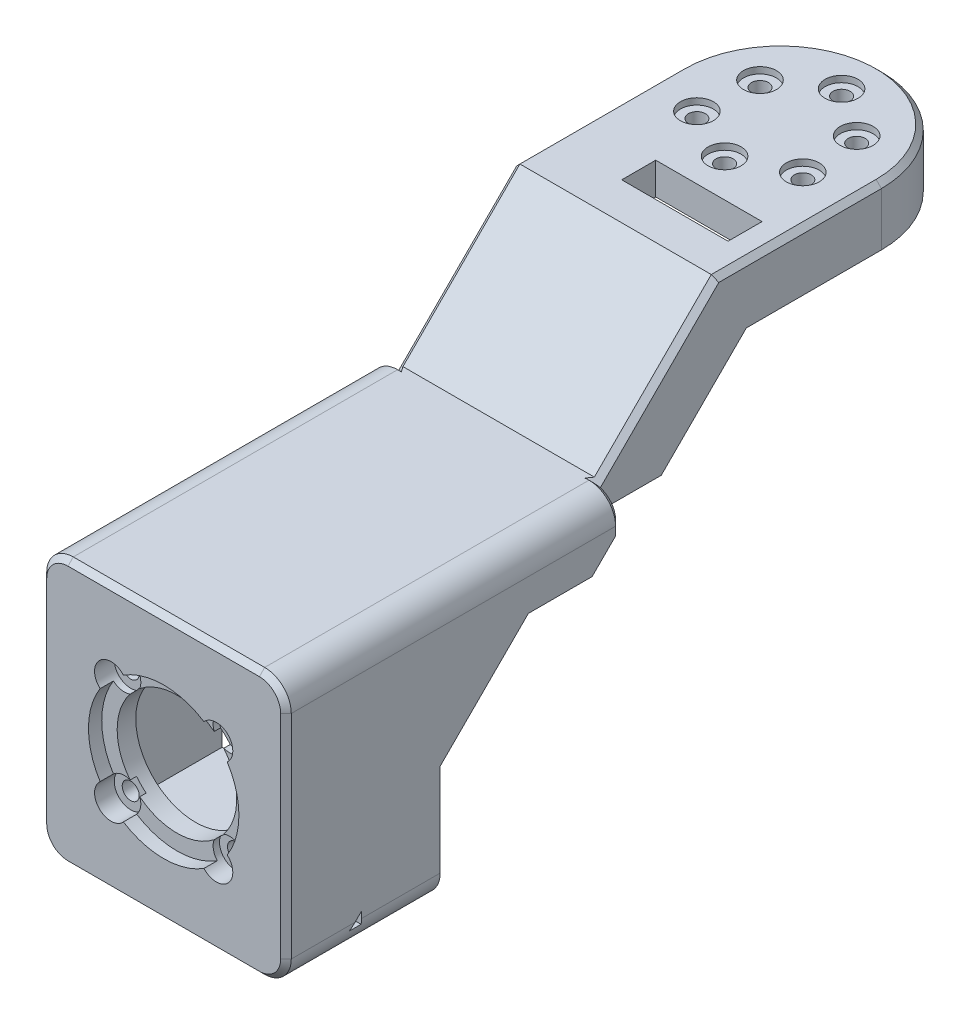
SolidWorks part; units mm, degrees
ref_plane "前视基准面" through (0, 0, 0) normal (0, 0, 1) x (1, 0, 0)
ref_plane "上视基准面" through (0, 0, 0) normal (0, 1, 0) x (1, 0, 0)
ref_plane "右视基准面" through (0, 0, 0) normal (1, 0, 0) x (0, 0, -1)
other "Configuration Table"
sketch "草图1" plane through (0, 0, 0) normal (0, 1, 0) x (1, 0, 0)
  circle A0 centre (0, 0) radius 19
  dimension "D1" = 38
extrude "凸台-拉伸1" add sketch "草图1" along normal blind 6
sketch "草图2" plane through (0, 6, 0) normal (0, 1, 0) x (1, 0, 0)
  line L0 (-19, 0) -> (19, 0) construction
  line L2 (-19, 0) -> (19, 0)
  line L3 (-19, 0) -> (-19, -25)
  line L4 (-19, -25) -> (19, -25)
  line L5 (19, 0) -> (19, -25)
  circle A0 centre (0, 0) radius 19 construction
  dimension "D1" = 25
extrude "凸台-拉伸2" add sketch "草图2" against normal up to surface (6 mm away) up to face at (0, 0, 19)
sketch "草图3" plane through (0, 6, 0) normal (0, 1, 0) x (1, 0, 0)
  line L1 (-19, -25) -> (19, -25)
  line L2 (-19, -25) -> (-19, -31)
  line L3 (-19, -31) -> (19, -31)
  line L4 (19, -25) -> (19, -31)
  dimension "D1" = 6
extrude "凸台-拉伸3" add sketch "草图3" against normal blind 28
sketch "草图4" plane through (0, 0, 31) normal (0, 0, 1) x (1, 0, 0)
  line L0 (19, -22) -> (19, 6) construction
  line L1 (-19, -22) -> (19, -22)
  line L2 (-19, -22) -> (-19, -16)
  line L3 (-19, -16) -> (19, -16)
  line L4 (19, -22) -> (19, -16)
  dimension "D1" = 6
extrude "凸台-拉伸4" add sketch "草图4" along normal blind 85
sketch "草图5" plane through (0, -22, 0) normal (0, -1, 0) x (1, 0, 0)
  line L0 (19, 116) -> (19, 25) construction
  line L1 (-19, 116) -> (19, 116)
  line L2 (-19, 116) -> (-19, 110)
  line L3 (-19, 110) -> (19, 110)
  line L4 (19, 116) -> (19, 110)
  dimension "D1" = 6
extrude "凸台-拉伸5" add sketch "草图5" along normal blind 40
sketch "草图6" plane through (0, 0, 0) normal (0, -1, 0) x (1, 0, 0)
  line L0 (-14.15, 0) -> (-14.15, 25)
  line L1 (19, 25) -> (-19, 25) construction
  line L2 (14.15, 0) -> (14.15, 25)
  line L3 (14.15, 25) -> (-14.15, 25)
  circle A0 centre (0, 0) radius 14.15
  arc M2 (-19, 0) -> (19, 0) centre (0, 0) ccw
  line M3 (19, 0) -> (19, 25)
  line M4 (19, 25) -> (-19, 25)
  line M5 (-19, 25) -> (-19, 0)
  dimension "D1" = 28.3
extrude "凸台-拉伸6" add sketch "草图6" along normal blind 6 contours A0 L0 L2 M4 M5 M2 M3 region at (0, 0, -14.7314)
sketch "草图7" plane through (-19, 0, 0) normal (-1, 0, 0) x (0, 0, 1)
  line L0 (31, 6) -> (53, -16)
  line L1 (116, -16) -> (31, -16) construction
  line L2 (53, -16) -> (31, -16)
  line L3 (31, -16) -> (31, 6)
sketch "草图8" plane through (19, 0, 0) normal (1, 0, 0) x (0, 0, -1)
  line L3 (-31, 6) -> (-53, -16)
  line L4 (-53, -16) -> (-31, -16)
  line L5 (-31, -16) -> (-31, 6)
  line L6 (-31, 6) -> (-53, -16)
  line L7 (-53, -16) -> (-31, -16)
  line L8 (-31, -16) -> (-31, 6)
  dimension "D1" = 0
extrude "凸台-拉伸8" add sketch "草图8" against normal up to surface (38 mm away) up to face at (-19, -20, 56.4)
sketch "草图11" plane through (0, 0, 110) normal (0, 0, -1) x (-1, 0, 0)
  line L0 (0, -22) -> (0, -41.5) construction
  line L1 (19, -22) -> (-19, -22) construction
  circle A0 centre (0, -41.5) radius 11.25
  dimension "D2" = 22.5
  dimension "D1" = 19.5
extrude "切除-拉伸2" cut sketch "草图11" against normal through all
sketch "草图12" plane through (0, 0, 116) normal (0, 0, 1) x (1, 0, 0)
  line L0 (0, -41.5) -> (9.8995, -31.6005) construction
  line L1 (0, -41.5) -> (14.2465, -41.5) construction
  circle A0 centre (9.8995, -31.6005) radius 1.6
  circle A1 centre (9.8995, -51.3995) radius 1.6
  circle A2 centre (-9.8995, -51.3995) radius 1.6
  circle A3 centre (-9.8995, -31.6005) radius 1.6
  point P13 (0, -41.5)
  dimension "D2" = 3.2
  dimension "D1" = 14
  dimension "D4" = 45
  dimension "D3" = 4
extrude "切除-拉伸3" cut sketch "草图12" against normal through all
sketch "草图13" plane through (0, 0, 116) normal (0, 0, 1) x (1, 0, 0)
  line L0 (0, -41.5) -> (11.25, -41.5) construction
  circle A0 centre (-9.8995, -31.6005) radius 3.1
  circle A1 centre (0, -41.5) radius 11.25 construction
  circle A2 centre (9.8995, -31.6005) radius 3.1
  circle A3 centre (9.8995, -51.3995) radius 3.1
  circle A4 centre (-9.8995, -51.3995) radius 3.1
  point P17 (0, -41.5)
  dimension "D1" = 6.2
  dimension "D2" = 4
extrude "切除-拉伸4" cut sketch "草图13" against normal blind 3.7
sketch "草图14" plane through (0, 0, 116) normal (0, 0, 1) x (1, 0, 0)
  circle A0 centre (0, -41.5) radius 14.15
  dimension "D1" = 28.3
extrude "切除-拉伸5" cut sketch "草图14" against normal blind 2.5
sketch "草图15" plane through (19, 0, 0) normal (1, 0, 0) x (0, 0, -1)
  line L0 (-110, -22) -> (-110, -62) construction
  line L2 (-110, -62) -> (-104, -62)
  line L3 (-104, -62) -> (-70, -28)
  line L4 (-70, -28) -> (-70, -22)
  line L5 (-110, -22) -> (-25, -22) construction
  line L6 (-70, -22) -> (-110, -22) construction
  line L7 (-110, -62) -> (-116, -62)
  line L8 (-116, -62) -> (-116, -16)
  line L9 (-116, -16) -> (-53, -16) construction
  line L10 (-116, -16) -> (-70, -16)
  line L11 (-70, -16) -> (-70, -22)
  dimension "D1" = 6
extrude "凸台-拉伸12" add sketch "草图15" along normal blind 4
sketch "草图16" plane through (-19, 0, 0) normal (-1, 0, 0) x (0, 0, 1)
  line L7 (104, -62) -> (110, -62)
  line L8 (70, -28) -> (104, -62)
  line L9 (70, -22) -> (70, -28)
  line L10 (70, -16) -> (70, -22)
  line L11 (116, -16) -> (70, -16)
  line L12 (116, -62) -> (116, -16)
  line L13 (110, -62) -> (116, -62)
  line L14 (104, -62) -> (110, -62)
  line L15 (70, -28) -> (104, -62)
  line L16 (70, -22) -> (70, -28)
  line L17 (70, -16) -> (70, -22)
  line L18 (116, -16) -> (70, -16)
  line L19 (116, -62) -> (116, -16)
  line L20 (110, -62) -> (116, -62)
  dimension "D1" = 0
extrude "凸台-拉伸13" add sketch "草图16" along normal blind 4
sketch "草图18" plane through (-19, 0, 0) normal (-1, 0, 0) x (0, 0, 1)
  line L1 (25, -6) -> (41, -22)
  line L2 (25, -22) -> (70, -22) construction
  line L3 (31, 6) -> (53, -16) construction
  line L4 (41, -22) -> (41.8531, -34.2873)
  line L5 (41.8531, -34.2873) -> (18.4073, -35.915)
  line L6 (18.4073, -35.915) -> (21.1184, -13.0175)
  line L7 (21.1184, -13.0175) -> (25, -6)
extrude "切除-拉伸7" cut sketch "草图18" against normal through all
sketch "草图19" plane through (0, -62, 0) normal (0, -1, 0) x (1, 0, 0)
  line L0 (23, 104) -> (23, 70) construction
  line L1 (-23, 116) -> (23, 116)
  line L2 (-23, 116) -> (-23, 86)
  line L3 (-23, 86) -> (23, 86)
  line L4 (23, 116) -> (23, 86)
  dimension "D1" = 30
extrude "凸台-拉伸14" add sketch "草图19" along normal blind 4
sketch "草图20" plane through (-23, 0, 0) normal (-1, 0, 0) x (0, 0, 1)
  line L1 (86, -66) -> (102.3181, -66)
  line L2 (86, -66) -> (86, -36.6886)
  line L3 (86, -36.6886) -> (102.3181, -36.6886)
  line L4 (102.3181, -66) -> (102.3181, -36.6886)
extrude "凸台-拉伸15" add sketch "草图20" against normal up to surface (4 mm away) up to face at (-19, -39.2, 92.8)
sketch "草图21" plane through (23, 0, 0) normal (1, 0, 0) x (0, 0, -1)
  line L1 (-86, -66) -> (-101.783, -66)
  line L2 (-86, -66) -> (-86, -39.6316)
  line L3 (-86, -39.6316) -> (-101.783, -39.6316)
  line L4 (-101.783, -66) -> (-101.783, -39.6316)
extrude "凸台-拉伸16" add sketch "草图21" against normal up to surface (4 mm away) up to face at (19, -39.2, 92.8)
sketch "草图22" plane through (-19, 0, 0) normal (-1, 0, 0) x (0, 0, 1)
  line L1 (70, -28) -> (53, -28)
  line L2 (70, -28) -> (70, -16)
  line L3 (70, -16) -> (53, -16)
  line L4 (53, -28) -> (53, -16)
  line L5 (70, -16) -> (70, -28) construction
  line L6 (70, -16) -> (70, -28) construction
extrude "凸台-拉伸17" add sketch "草图22" along normal up to surface (4 mm away) up to face at (-23, -39.3333, 90.6667)
chamfer "倒角1" distance 5 angle 45 1 edges at (-21, -28, 53)
sketch "草图23" plane through (19, 0, 0) normal (1, 0, 0) x (0, 0, -1)
  line L0 (-70, -16) -> (-53, -16) construction
  line L1 (-70, -28) -> (-53, -28)
  line L2 (-70, -28) -> (-70, -16)
  line L3 (-70, -16) -> (-53, -16)
  line L4 (-53, -28) -> (-53, -16)
extrude "凸台-拉伸18" add sketch "草图23" along normal up to surface (4 mm away) up to face at (23, -39.3333, 90.6667)
chamfer "倒角2" distance 5 angle 45 1 edges at (21, -28, 53)
sketch "草图24" plane through (0, 0, 0) normal (0, -1, 0) x (1, 0, 0)
  line L0 (0, 0) -> (0, 10.5) construction
  line L1 (0, 0) -> (9.9593, 5.75) construction
  circle A0 centre (0, 10.5) radius 1.6
  circle A1 centre (9.0933, -5.25) radius 1.6
  circle A2 centre (-9.0933, -5.25) radius 1.6
  circle A3 centre (9.9593, 5.75) radius 1.6
  circle A4 centre (0, -11.5) radius 1.6
  circle A5 centre (-9.9593, 5.75) radius 1.6
  point P10 (0, 0)
  point P18 (0, 0)
  dimension "D1" = 3.2
  dimension "D6" = 3.2
  dimension "D2" = 10.5
  dimension "D4" = 60
  dimension "D5" = 11.5
  dimension "D3" = 3
  dimension "D7" = 3
extrude "切除-拉伸8" cut sketch "草图24" against normal through all
sketch "草图25" plane through (0, 6, 0) normal (0, 1, 0) x (1, 0, 0)
  circle A0 centre (0, 11.5) radius 3.1
  circle A1 centre (-9.0933, 5.25) radius 3.1
  circle A2 centre (-9.9593, -5.75) radius 3.1
  circle A3 centre (0, -10.5) radius 3.1
  circle A4 centre (9.9593, -5.75) radius 3.1
  circle A5 centre (9.0933, 5.25) radius 3.1
  dimension "D1" = 6.2
extrude "切除-拉伸9" cut sketch "草图25" against normal blind 1.2
fillet "圆角1" radius 5 4 edges at (23, -16, 84.5) (-23, -16, 84.5) (-23, -66, 101) (23, -66, 101)
chamfer "倒角3" distance 1 angle 45 31 edges at (-23, -25.5, 55.5) (-23, -28, 64) (-23, -36, 78) (-19, -22, 47) (-19, -14, 33) (-19, -5.0505, 42.0505) (-19, 6, 15.5) (0, 6, -19) (19, 6, 15.5) (19, -5.0505, 42.0505) (-19, -6, 12.5) (0, -6, -19) (19, -6, 12.5) (19, -14, 33) (19, -22, 47) (23, -25.5, 55.5) (23, -28, 64) (23, -36, 78) (-23, -52.5, 86) (23, -52.5, 86) (-21.5355, -64.5355, 86) (21.5355, -64.5355, 86) (0, -66, 86) (0, -16, 116) (21.5355, -17.4645, 116) (-21.5355, -17.4645, 116) (23, -41, 116) (-23, -41, 116) (21.5355, -64.5355, 116) (-21.5355, -64.5355, 116) (0, -66, 116)
chamfer "倒角4" distance 1 angle 45 4 edges at (23, -21.2929, 53) (21.5355, -17.4645, 53) (-23, -21.2929, 53) (-21.5355, -17.4645, 53)
sketch "草图26" plane through (0, 0, 0) normal (0, -1, 0) x (1, 0, 0)
  line L0 (14.15, 0) -> (14.15, 25) construction
  line L1 (-14.15, 25) -> (14.15, 25)
  line L2 (-14.15, 25) -> (-14.15, 24)
  line L3 (-14.15, 24) -> (14.15, 24)
  line L4 (14.15, 25) -> (14.15, 24)
  dimension "D1" = 1
extrude "凸台-拉伸19" add sketch "草图26" along normal up to surface (6 mm away) up to face at (0, -6, 8.4813)
sketch "草图27" plane through (0, 0, 24) normal (0, 0, -1) x (-1, 0, 0)
  circle A0 centre (-9, -2.5) radius 1.175 construction
  circle A1 centre (0.5, -2.5) radius 1.175 construction
  circle A2 centre (-9, -2.5) radius 1.175 construction
  circle A3 centre (0.5, -2.5) radius 1.175 construction
  circle A4 centre (-9, -2.5) radius 1.35
  circle A5 centre (0.5, -2.5) radius 1.35
  dimension "D1" = 2.7
extrude "切除-拉伸10" cut sketch "草图27" against normal blind 2.5
sketch "草图28" plane through (0, 0, 0) normal (0, -1, 0) x (1, 0, 0)
  line L0 (14.15, 24) -> (-5.85, 24)
  line L1 (14.15, 24) -> (14.15, 17.6)
  line L2 (-5.85, 24) -> (-5.85, 17.6)
  line L3 (14.15, 17.6) -> (-5.85, 17.6)
  dimension "D1" = 6.4
  dimension "D2" = 20
extrude "切除-拉伸11" cut sketch "草图28" against normal through all
